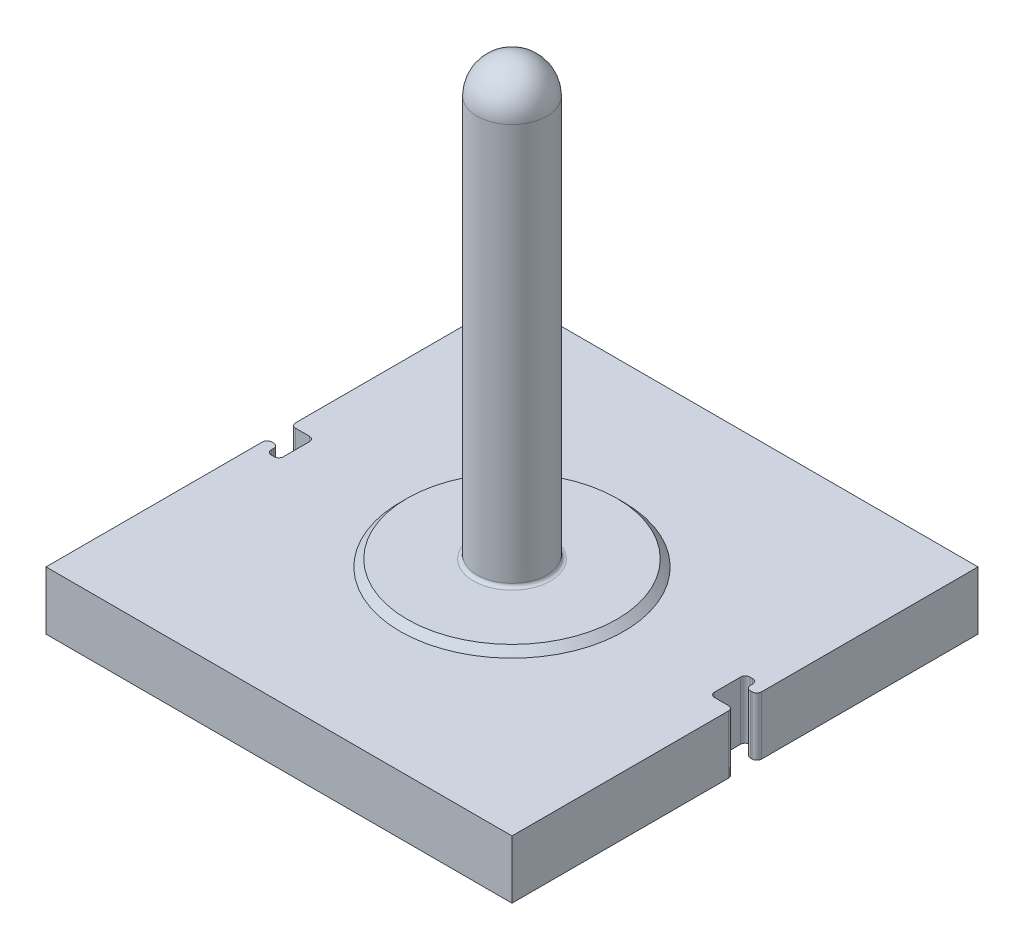
SolidWorks part; units mm, degrees
material "Custom Plastic"
ref_plane "Front Plane" through (0, 0, 0) normal (0, 0, 1) x (1, 0, 0)
ref_plane "Top Plane" through (0, 0, 0) normal (0, 1, 0) x (1, 0, 0)
ref_plane "Right Plane" through (0, 0, 0) normal (1, 0, 0) x (0, 0, -1)
sketch "Sketch1" plane through (0, 0, 0) normal (0, 1, 0) x (1, 0, 0)
  line L1 (-100, 100) -> (100, 100)
  line L2 (-100, 100) -> (-100, -100)
  line L3 (-100, -100) -> (100, -100)
  line L4 (100, 100) -> (100, -100)
  line L5 (-100, 100) -> (100, -100) construction
  line L6 (-100, -100) -> (100, 100) construction
  point P0 (0, 0)
  dimension "D1" = 200
  dimension "D2" = 200
extrude "Boss-Extrude1" add sketch "Sketch1" along normal blind 25
sketch "Sketch2" plane through (0, 25, 0) normal (0, 1, 0) x (1, 0, 0)
  circle A0 centre (0, 0) radius 15
  dimension "D1" = 30
extrude "Boss-Extrude2" add sketch "Sketch2" along normal blind 190
sketch "Sketch3" plane through (0, 0, 0) normal (0, 1, 0) x (1, 0, 0)
  line L0 (-1000, 0) -> (49000, 0) construction
  line L1 (-100, 100) -> (-100, -100) construction
  line L2 (-100, 100) -> (-100, -100) construction
  line L3 (-100, 5.1) -> (-92, 5.1)
  line L4 (-90, 3.1) -> (-90, -8.1)
  line L5 (-92, -10.1) -> (-93.2, -10.1)
  line L6 (-95.2, -8.1) -> (-95.2, -7.1)
  line L7 (-97.2, -5.1) -> (-100, -5.1)
  line L8 (-100, -5.1) -> (-100, 5.1)
  line L9 (100, -100) -> (100, 100) construction
  line L10 (100, -100) -> (100, 100) construction
  line L17 (100, -5.1) -> (92, -5.1)
  line L18 (90, -3.1) -> (90, 8.1)
  line L19 (92, 10.1) -> (93.2, 10.1)
  line L20 (95.2, 8.1) -> (95.2, 7.1)
  line L21 (97.2, 5.1) -> (100, 5.1)
  line L22 (100, 5.1) -> (100, -5.1)
  arc A0 (-92, 5.1) -> (-90, 3.1) centre (-92, 3.1) cw
  arc A1 (-90, -8.1) -> (-92, -10.1) centre (-92, -8.1) cw
  arc A2 (-93.2, -10.1) -> (-95.2, -8.1) centre (-93.2, -8.1) cw
  arc A3 (-95.2, -7.1) -> (-97.2, -5.1) centre (-97.2, -7.1) ccw
  arc A8 (95.2, 7.1) -> (97.2, 5.1) centre (97.2, 7.1) ccw
  arc A9 (93.2, 10.1) -> (95.2, 8.1) centre (93.2, 8.1) cw
  arc A10 (90, 8.1) -> (92, 10.1) centre (92, 8.1) cw
  arc A11 (92, -5.1) -> (90, -3.1) centre (92, -3.1) cw
  point P7 (-100, 0)
  point P15 (-90, 5.1)
  point P18 (-90, -10.1)
  point P21 (-95.2, -10.1)
  point P24 (-95.2, -5.1)
  point P28 (100, 0)
  point P36 (95.2, 5.1)
  point P39 (95.2, 10.1)
  point P42 (90, 10.1)
  point P45 (90, -5.1)
  dimension "D5" = 2
  dimension "D10" = 2
  dimension "D1" = 10.2
  dimension "D2" = 15.2
  dimension "D3" = 4.8
  dimension "D4" = 5.2
  dimension "D6" = 10.2
  dimension "D7" = 15.2
  dimension "D8" = 4.8
  dimension "D9" = 5.2
extrude "Cut-Extrude3" cut sketch "Sketch3" along normal up to next
fillet "Fillet2" radius 2 4 edges at (-100, 12.5, 5.1) (-100, 12.5, -5.1) (100, 12.5, 5.1) (100, 12.5, -5.1)
fillet "Fillet3" radius 15 1 edges at (0, 215, 15)
sketch "Sketch4" plane through (0, 25, 0) normal (0, 1, 0) x (1, 0, 0)
  circle A0 centre (0, 0) radius 45
  dimension "D1" = 90
extrude "Boss-Extrude3" add sketch "Sketch4" along normal blind 3
chamfer "Chamfer1" distance 3 angle 45 1 edges at (0, 25, 45)
fillet "Fillet4" radius 1.5 1 edges at (0, 28, 15)
